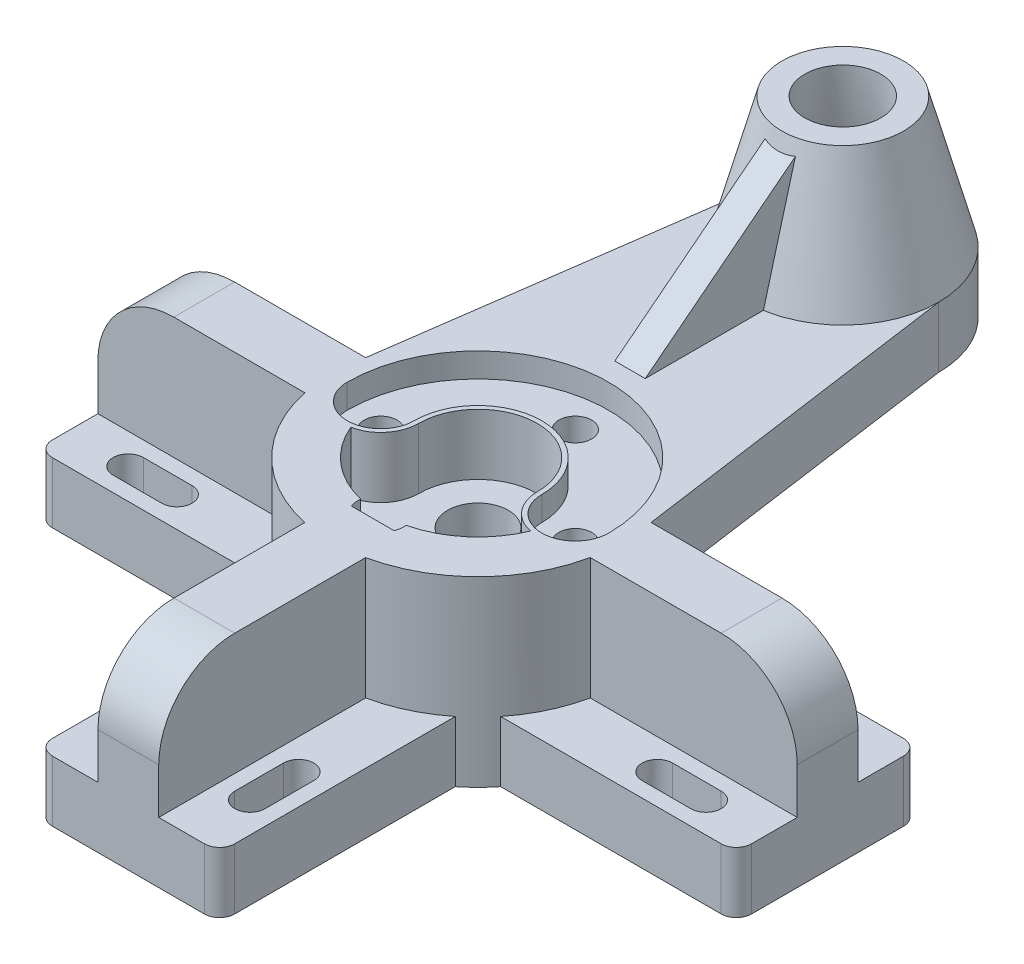
SolidWorks part; units mm, degrees
ref_plane "Front Plane" through (0, 0, 0) normal (0, 0, 1) x (1, 0, 0)
ref_plane "Top Plane" through (0, 0, 0) normal (0, 1, 0) x (1, 0, 0)
ref_plane "Right Plane" through (0, 0, 0) normal (1, 0, 0) x (0, 0, -1)
sketch "Sketch3" plane through (0, 0, 0) normal (0, 1, 0) x (1, 0, 0)
  circle A0 centre (0, 0) radius 48
  circle A1 centre (0, 0) radius 10
  dimension "D1" = 96
  dimension "D2" = 20
extrude "Boss-Extrude3" add sketch "Sketch3" along normal blind 60 contours A0
sketch "Sketch4" plane through (0, 60, 0) normal (0, 1, 0) x (1, 0, 0)
  circle A0 centre (0, 0) radius 10
  dimension "D1" = 20
extrude "Cut-Extrude2" cut sketch "Sketch4" against normal blind 60
sketch "Sketch5" plane through (0, 60, 0) normal (0, 1, 0) x (1, 0, 0)
  circle A0 centre (0, 0) radius 32
  dimension "D1" = 64
extrude "Cut-Extrude3" cut sketch "Sketch5" against normal blind 20
sketch "Sketch6" plane through (0, 60, 0) normal (0, 1, 0) x (1, 0, 0)
  circle A0 centre (0, 32) radius 7.5
  circle A1 centre (0, 0) radius 32 construction
  circle A2 centre (0, 0) radius 32 construction
  dimension "D1" = 15
extrude "Cut-Extrude4" cut sketch "Sketch6" against normal blind 8
mirror "Mirror1" about plane through (0, 0, 0) normal (0, 0, 1) of "Cut-Extrude4"
sketch "Sketch7" plane through (0, 60, 0) normal (0, 1, 0) x (1, 0, 0)
  circle A0 centre (-32, 0) radius 7.5
  arc A1 (-7.4483, 31.1211) -> (-7.4483, -31.1211) centre (0, 0) ccw construction
  dimension "D1" = 15
extrude "Cut-Extrude5" cut sketch "Sketch7" against normal blind 8
mirror "Mirror2" about plane through (0, 0, 0) normal (1, 0, 0) of "Cut-Extrude5"
sketch "Sketch8" plane through (0, 52, 0) normal (0, 1, 0) x (1, 0, 0)
  circle A0 centre (0, 32) radius 5.4
  arc A1 (7.4483, 31.1211) -> (-7.4483, 31.1211) centre (0, 0) ccw construction
  arc A2 (31.1211, -7.4483) -> (31.1211, 7.4483) centre (0, 0) ccw construction
  circle A3 centre (32, 0) radius 5.4
  circle A4 centre (-32, 0) radius 5.4
  arc A5 (-31.1211, 7.4483) -> (-31.1211, -7.4483) centre (0, 0) ccw construction
  circle A6 centre (0, -32) radius 5.4
  arc A7 (-7.4483, -31.1211) -> (7.4483, -31.1211) centre (0, 0) ccw construction
  dimension "D1" = 10.8
  dimension "D2" = 10.8
  dimension "D3" = 10.8
  dimension "D4" = 10.8
extrude "Cut-Extrude6" cut sketch "Sketch8" against normal blind 31.25
sketch "Sketch9" plane through (0, 0, 0) normal (0, -1, 0) x (1, 0, 0)
  line L0 (0, 0) -> (0, 115) construction
  line L2 (-30, 115) -> (30, 115)
  line L3 (-30, 115) -> (-30, 34.5689)
  line L4 (-30, 34.5689) -> (30, 34.5689)
  line L5 (30, 115) -> (30, 34.5689)
  dimension "D1" = 115
  dimension "D2" = 60
extrude "Boss-Extrude6" add sketch "Sketch9" against normal blind 20 contours L5 L4 L3 L2
sketch "Sketch10" plane through (0, 0, 0) normal (0, -1, 0) x (1, 0, 0)
  line L0 (-30, 115) -> (30, 115) construction
  line L1 (-10, 115) -> (10, 115)
  line L2 (-10, 115) -> (-10, 34.611)
  line L3 (-10, 34.611) -> (10, 34.611)
  line L4 (10, 115) -> (10, 34.611)
  line L5 (0, 0) -> (0, 127.8911) construction
  dimension "D1" = 20
extrude "Boss-Extrude9" add sketch "Sketch10" against normal blind 60 contours L2 L3 L4 L1
fillet "Fillet1" radius 25 1 edges at (0, 60, 115)
sketch "Sketch11" plane through (0, 0, 0) normal (0, -1, 0) x (1, 0, 0)
  line L0 (0, 0) -> (134.6765, 0) construction
  line L1 (0, 0) -> (-115, 0) construction
  line L3 (-115.0241, -30) -> (-34.6806, -30)
  line L4 (-115.0241, -30) -> (-115.0241, 30)
  line L5 (-115.0241, 30) -> (-34.6806, 30)
  line L6 (-34.6806, -30) -> (-34.6806, 30)
  line L7 (115, -30) -> (34.3916, -30)
  line L8 (115, -30) -> (115, 30)
  line L9 (115, 30) -> (34.3916, 30)
  line L10 (34.3916, -30) -> (34.3916, 30)
  dimension "D1" = 115
  dimension "D2" = 115
  dimension "D3" = 60
  dimension "D4" = 60
extrude "Boss-Extrude10" add sketch "Sketch11" against normal blind 20
sketch "Sketch12" plane through (0, 0, 0) normal (0, -1, 0) x (1, 0, 0)
  line L0 (0, 0) -> (-115.0241, 0) construction
  line L1 (-115.0241, 30) -> (-115.0241, -30) construction
  line L2 (0, 0) -> (115, 0) construction
  line L3 (115, -30) -> (115, 30) construction
  line L5 (-115.0241, -10) -> (-37.8301, -10)
  line L6 (-115.0241, -10) -> (-115.0241, 10)
  line L7 (-115.0241, 10) -> (-37.8301, 10)
  line L8 (-37.8301, -10) -> (-37.8301, 10)
  line L9 (115, -10) -> (40.3272, -10)
  line L10 (115, -10) -> (115, 10)
  line L11 (115, 10) -> (40.3272, 10)
  line L12 (40.3272, -10) -> (40.3272, 10)
  dimension "D1" = 20
  dimension "D2" = 20
extrude "Boss-Extrude11" add sketch "Sketch12" against normal blind 60
fillet "Fillet2" radius 25 1 edges at (-115.0241, 60, 0)
fillet "Fillet3" radius 25 1 edges at (115, 60, 0)
sketch "Sketch13" plane through (0, 20, 0) normal (0, 1, 0) x (1, 0, 0)
  line L0 (20, -95) -> (20, -79) construction
  line L1 (15, -95) -> (15, -79)
  line L2 (25, -95) -> (25, -79)
  line L3 (30, -115) -> (30, -37.47) construction
  line L4 (10, -115) -> (30, -115) construction
  arc A0 (15, -95) -> (25, -95) centre (20, -95) ccw
  arc A1 (25, -79) -> (15, -79) centre (20, -79) ccw
  point P2 (20, -87)
  dimension "D2" = 5
  dimension "D1" = 16
  dimension "D3" = 10
  dimension "D4" = 20
extrude "Cut-Extrude7" cut sketch "Sketch13" against normal blind 20
mirror "Mirror7" about plane through (0, 20, 0) normal (0, 1, 0) of "Cut-Extrude7"
sketch "Sketch15" plane through (0, 20, 0) normal (0, 1, 0) x (1, 0, 0)
  line L0 (-20, -79) -> (-20, -95) construction
  line L1 (-15, -79) -> (-15, -95)
  line L2 (-25, -79) -> (-25, -95)
  line L3 (-30, -115) -> (-10, -115) construction
  line L4 (-30, -115) -> (-30, -37.47) construction
  arc A0 (-15, -79) -> (-25, -79) centre (-20, -79) ccw
  arc A1 (-25, -95) -> (-15, -95) centre (-20, -95) ccw
  point P2 (-20, -87)
  dimension "D2" = 5
  dimension "D1" = 16
  dimension "D3" = 20
  dimension "D4" = 10
extrude "Cut-Extrude8" cut sketch "Sketch15" against normal blind 20
sketch "Sketch17" plane through (0, 20, 0) normal (0, 1, 0) x (1, 0, 0)
  line L0 (-95.0241, -20) -> (-79.0241, -20) construction
  line L1 (-95.0241, -15) -> (-79.0241, -15)
  line L2 (-95.0241, -25) -> (-79.0241, -25)
  line L3 (-37.47, -30) -> (-115.0241, -30) construction
  line L4 (-115.0241, -30) -> (-115.0241, -10) construction
  arc A0 (-95.0241, -15) -> (-95.0241, -25) centre (-95.0241, -20) ccw
  arc A1 (-79.0241, -25) -> (-79.0241, -15) centre (-79.0241, -20) ccw
  point P2 (-87.0241, -20)
  dimension "D2" = 5
  dimension "D1" = 10
  dimension "D3" = 16
  dimension "D4" = 20
extrude "Cut-Extrude9" cut sketch "Sketch17" against normal blind 20
sketch "Sketch18" plane through (0, 20, 0) normal (0, 1, 0) x (1, 0, 0)
  line L0 (-95.0241, 20) -> (-79.0241, 20) construction
  line L1 (-95.0241, 25) -> (-79.0241, 25)
  line L2 (-95.0241, 15) -> (-79.0241, 15)
  line L3 (-115.0241, 10) -> (-115.0241, 30) construction
  line L4 (-115.0241, 30) -> (-37.47, 30) construction
  arc A0 (-95.0241, 25) -> (-95.0241, 15) centre (-95.0241, 20) ccw
  arc A1 (-79.0241, 15) -> (-79.0241, 25) centre (-79.0241, 20) ccw
  point P2 (-87.0241, 20)
  dimension "D2" = 5
  dimension "D1" = 16
  dimension "D3" = 20
  dimension "D4" = 10
extrude "Cut-Extrude10" cut sketch "Sketch18" against normal blind 20
sketch "Sketch19" plane through (0, 20, 0) normal (0, 1, 0) x (1, 0, 0)
  line L0 (79, 20) -> (95, 20) construction
  line L1 (79, 25) -> (95, 25)
  line L2 (79, 15) -> (95, 15)
  line L3 (115, 30) -> (115, 10) construction
  line L4 (37.47, 30) -> (115, 30) construction
  arc A0 (79, 25) -> (79, 15) centre (79, 20) ccw
  arc A1 (95, 15) -> (95, 25) centre (95, 20) ccw
  point P2 (87, 20)
  dimension "D2" = 5
  dimension "D1" = 16
  dimension "D3" = 20
  dimension "D4" = 10
extrude "Cut-Extrude11" cut sketch "Sketch19" against normal blind 20
sketch "Sketch20" plane through (0, 20, 0) normal (0, 1, 0) x (1, 0, 0)
  line L0 (79, -20) -> (95, -20) construction
  line L1 (79, -15) -> (95, -15)
  line L2 (79, -25) -> (95, -25)
  line L3 (115, -30) -> (37.47, -30) construction
  line L4 (115, -10) -> (115, -30) construction
  arc A0 (79, -15) -> (79, -25) centre (79, -20) ccw
  arc A1 (95, -25) -> (95, -15) centre (95, -20) ccw
  point P2 (87, -20)
  dimension "D1" = 5
  dimension "D2" = 16
  dimension "D3" = 10
  dimension "D4" = 20
extrude "Cut-Extrude12" cut sketch "Sketch20" against normal blind 20
sketch "Sketch21" plane through (0, 60, 0) normal (0, 1, 0) x (1, 0, 0)
  line L0 (0, 0) -> (0, 120) construction
  line L1 (-46.9468, 10) -> (-31.5, 120)
  line L2 (46.9468, 10) -> (31.5, 120)
  circle A0 centre (0, 120) radius 31.5
  arc A1 (46.9468, 10) -> (-46.9468, 10) centre (0, 0) ccw construction
  arc A2 (46.9468, 10) -> (-46.9468, 10) centre (0, 0) ccw
  arc M7 (46.9468, 10) -> (-46.9468, 10) centre (0, 0) ccw
  dimension "D1" = 63
  dimension "D2" = 120
extrude "Boss-Extrude12" add sketch "Sketch21" against normal blind 20 contours L0 L2 A0 M7 | A2 L0 A0 L1 | A0 region at (-22.6048, 60, -66.8796) region at (22.6048, 60, -66.8796) region at (-21.6439, 60, -98.3561)
fillet "Fillet4" radius 5 1 edges at (-30, 10, 115)
fillet "Fillet5" radius 5 1 edges at (30, 10, 115)
fillet "Fillet6" radius 5 1 edges at (115, 10, 30)
fillet "Fillet7" radius 5 1 edges at (115, 10, -30)
fillet "Fillet8" radius 5 1 edges at (-115.0241, 10, 30)
fillet "Fillet9" radius 5 2 edges at (-115.0241, 10, -30) (-37.47, 10, -30)
sketch "Sketch23" plane through (0, 0, 0) normal (1, 0, 0) x (0, 0, -1)
  line L0 (120, 60) -> (120, 119.9802) construction
  line L1 (140, 103) -> (151.5, 60)
  line L2 (151.5, 60) -> (120, 60) construction
  dimension "D1" = 20
  dimension "D2" = 43
sketch "Sketch27" plane through (0, 60, 0) normal (0, 1, 0) x (1, 0, 0)
  circle A0 centre (0, 120) radius 31.5
ref_plane "Plane1" through (0, 103, 0) normal (0, 1, 0) x (1, 0, 0)
sketch "Sketch28" plane through (0, 103, 0) normal (0, 1, 0) x (1, 0, 0)
  circle A0 centre (0, 120) radius 20
  dimension "D1" = 40
sketch "Sketch29" plane through (0, 60, 0) normal (0, 1, 0) x (1, 0, 0)
  circle A0 centre (0, 120) radius 31.5
  dimension "D1" = 63
ref_plane "Plane2" through (0, 103, 0) normal (0, 1, 0) x (1, 0, 0)
sketch "Sketch30" plane through (0, 103, 0) normal (0, 1, 0) x (1, 0, 0)
  circle A0 centre (0, 120) radius 20
  dimension "D1" = 40
ref_plane "Plane3" through (0, 103, 0) normal (0, 1, 0) x (1, 0, 0)
sketch "Sketch31" plane through (0, 60, 0) normal (0, 1, 0) x (1, 0, 0)
  circle A0 centre (0, 120) radius 31.5
sketch "Sketch39" plane through (0, 60, 0) normal (0, 1, 0) x (1, 0, 0)
  arc A0 (-32, 0) -> (32, 0) centre (0, 0) cw construction
  arc A1 (44.5, 0) -> (-44.5, 0) centre (0, 0) ccw
  arc A2 (19.5, 0) -> (-19.5, 0) centre (0, 0) ccw
  arc A3 (19.5, 0) -> (44.5, 0) centre (32, 0) ccw
  arc A4 (-44.5, 0) -> (-19.5, 0) centre (-32, 0) ccw
  point P3 (0, 32)
  dimension "D1" = 12.5
extrude "Boss-Extrude14" add sketch "Sketch39" against normal blind 20
sketch "Sketch41" plane through (0, 60, 0) normal (0, 1, 0) x (1, 0, 0)
  arc A0 (-32, 0) -> (32, 0) centre (0, 0) cw construction
  arc A1 (43, 0) -> (-43, 0) centre (0, 0) ccw
  arc A2 (21, 0) -> (-21, 0) centre (0, 0) ccw
  arc A3 (21, 0) -> (43, 0) centre (32, 0) ccw
  arc A4 (-43, 0) -> (-21, 0) centre (-32, 0) ccw
  point P3 (0, 32)
  dimension "D4" = 11
  dimension "D1" = 32
  dimension "D2" = 32
  dimension "D3" = 32
extrude "Cut-Extrude15" cut sketch "Sketch41" against normal blind 8
sketch "Sketch43" plane through (0, 60, 0) normal (0, 1, 0) x (1, 0, 0)
  circle A0 centre (0, 32) radius 5.4
  circle A1 centre (32, 0) radius 5.4
  circle A2 centre (-32, 0) radius 5.4
  dimension "D3" = 10.8
  dimension "D4" = 10.8
  dimension "D5" = 10.8
  dimension "D1" = 32
  dimension "D2" = 32
extrude "Cut-Extrude16" cut sketch "Sketch43" against normal blind 31.25
sketch "Sketch44" plane through (0, 103, 0) normal (0, 1, 0) x (1, 0, 0)
  line L0 (0, 151.5) -> (0, 0) construction
  arc A0 (31.5, 120) -> (-31.5, 120) centre (0, 120) ccw construction
  circle A1 centre (0, 120) radius 31.5 construction
  circle A2 centre (0, 120) radius 20
  dimension "D1" = 63
  dimension "D2" = 40
sketch "Sketch45" plane through (0, 60, 0) normal (0, 1, 0) x (1, 0, 0)
  line L0 (0, 151.5) -> (0, 0) construction
  arc A0 (31.5, 120) -> (-31.5, 120) centre (0, 120) ccw construction
  circle A1 centre (0, 120) radius 31.5
loft "Loft1" add profiles "Sketch45", "Sketch44" connector at (0, 60, -88.5) connector at (0, 103, -100)
sketch "Sketch46" plane through (0, 103, 0) normal (0, 1, 0) x (1, 0, 0)
  circle A0 centre (0, 120) radius 12.5
  dimension "D1" = 25
sketch "Sketch47" plane through (0, 40, 0) normal (0, -1, 0) x (-1, 0, 0)
  circle A0 centre (0, 120) radius 22.5
  dimension "D1" = 45
loft "Cut-Loft1" cut profiles "Sketch47", "Sketch46" connector at (-18.5775, 40, -107.3064) connector at (0, 103, -107.5)
sketch "Sketch48" plane through (0, 0, 0) normal (1, 0, 0) x (0, 0, -1)
  line L0 (100, 103) -> (100, 98) construction
  line L2 (100, 103) -> (88.5, 60) construction
  line L3 (98.665, 98.0081) -> (50.0168, 60)
  line L4 (10, 60) -> (120, 60) construction
  dimension "D1" = 5
  dimension "D2" = 38
rib "Rib4" sketch "Sketch48" sketch "Sketch48" thickness 10 extrusion direction parallel to sketch draft on no parameters "D1"=10
